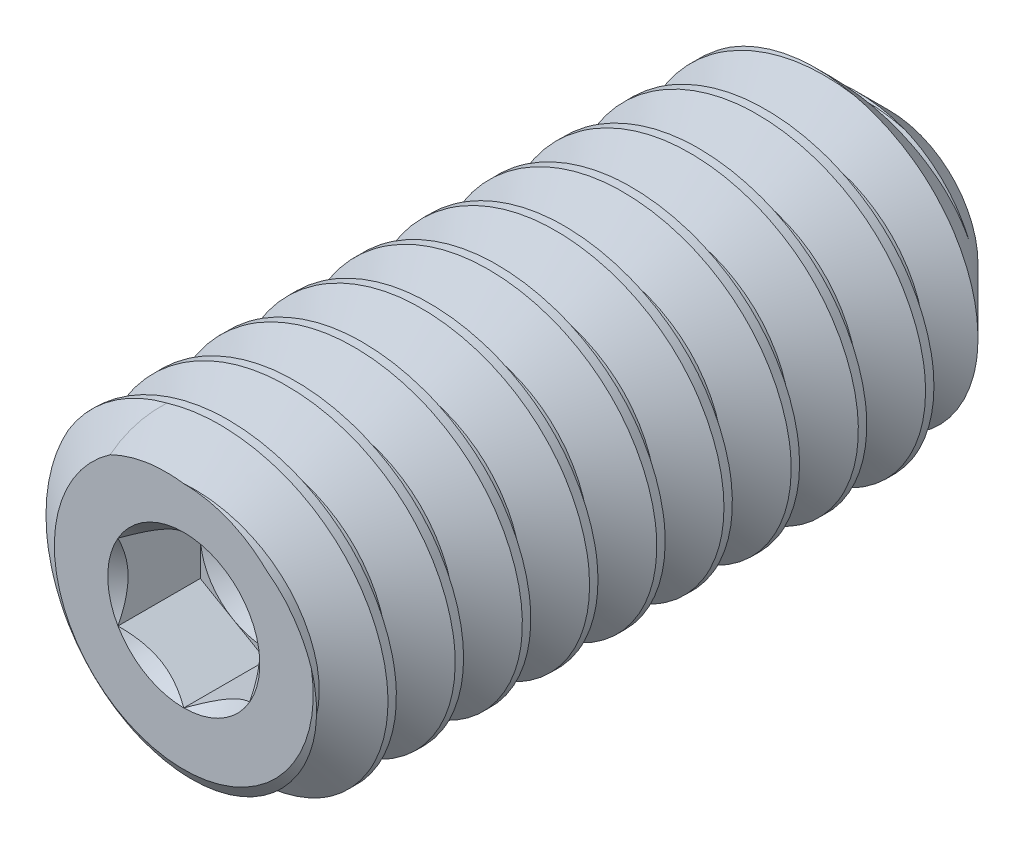
SolidWorks part; units mm, degrees
ref_plane "Front" through (0, 0, 0) normal (0, 0, 1) x (1, 0, 0)
ref_plane "Top" through (0, 0, 0) normal (0, 1, 0) x (1, 0, 0)
ref_plane "Right" through (0, 0, 0) normal (1, 0, 0) x (0, 0, -1)
sketch "Sketch22" plane through (0, 0, 0) normal (1, 0, 0) x (0, 0, -1)
  line L0 (-2.2014, 0) -> (-2.2014, 0.8738)
  line L1 (-2.2014, 0.8738) -> (-2.0485, 1.0922)
  line L2 (-2.0485, 1.0922) -> (2.0673, 1.0922)
  line L3 (2.0673, 1.0922) -> (2.5611, 0.5985)
  line L4 (2.5611, 0.5985) -> (2.2014, 0)
  line L5 (2.2014, 0) -> (-2.2014, 0)
  line L6 (2.2014, 0) -> (2.5611, 0) construction
  line L7 (2.5611, 0) -> (2.5611, 0.5985) construction
  line L8 (2.5611, -0.5985) -> (2.2014, 0) construction
  line L9 (-2.0485, -1.0922) -> (2.0673, -1.0922) construction
  dimension "Dia" = 2.1844
  dimension "Length" = 4.7625
  dimension "D3" = 35
  dimension "D5" = 118
  dimension "D6" = 45
  dimension "D7" = 1.7475
revolve "Revolve1" add sketch "Sketch22" angle 360 about L6
ref_plane "Plane1" through (0, 0, -2.5611) normal (0, 0, 1) x (1, 0, 0)
sketch "Sketch27" plane through (0, 0, -2.5611) normal (0, 0, 1) x (1, 0, 0)
  circle A0 centre (0, 0) radius 1.0922 construction
  circle A1 centre (0, 0) radius 1.0922
curve "Helix/Spiral1" pitch 0.4536 height 5.2161 radius 1.0922 centre (0, 0, -2.5611) axis (0, 0, 1) start towards (0, 1, 0)
sketch "Sketch28" plane through (0, 0, 0) normal (1, 0, 0) x (0, 0, -1)
  line L0 (2.5611, 1.0922) -> (2.9579, 1.0922)
  line L1 (2.9579, 1.0922) -> (2.7878, 0.7976)
  line L2 (2.7878, 0.7976) -> (2.7311, 0.7976)
  line L3 (2.7311, 0.7976) -> (2.5611, 1.0922)
  line L4 (2.6461, 0.9449) -> (2.8729, 0.9449) construction
  line L6 (-2.0485, 1.0922) -> (2.0673, 1.0922) construction
  line L7 (2.5611, 3.4925) -> (2.5611, -3.4925) construction
  dimension "D1" = 0.0567
  dimension "D2" = 0.2268
  dimension "D3" = 60
sweep "Cut-Sweep2" cut profiles "Sketch28" path "Helix/Spiral1"
sketch "Sketch23" plane through (0, 0, 2.2014) normal (0, 0, 1) x (1, 0, 0)
  line L1 (0, 0.5133) -> (-0.4445, 0.2566)
  line L2 (-0.4445, 0.2566) -> (-0.4445, -0.2566)
  line L3 (-0.4445, -0.2566) -> (0, -0.5133)
  line L4 (0, -0.5133) -> (0.4445, -0.2566)
  line L5 (0.4445, -0.2566) -> (0.4445, 0.2566)
  line L6 (0.4445, 0.2566) -> (0, 0.5133)
  circle A0 centre (0, 0) radius 0.4445 construction
  dimension "Hex" = 0.889
extrude "Cut-Extrude10" cut sketch "Sketch23" against normal blind 0.5556
sketch "Sketch24" plane through (0, 0, 2.2014) normal (0, 0, 1) x (1, 0, 0)
  circle A0 centre (0, 0) radius 0.5133
extrude "Cut-Extrude11" cut sketch "Sketch24" against normal through all draft 45
sketch "Sketch26" plane through (0, 0, 1.6458) normal (0, 0, 1) x (1, 0, 0)
  circle A0 centre (0, 0) radius 0.4445 construction
  circle A1 centre (0, 0) radius 0.4445
extrude "Cut-Extrude12" cut sketch "Sketch26" against normal through all draft 60
sketch "Sketch30" plane through (0, 0, 0) normal (1, 0, 0) x (0, 0, -1)
  line L0 (-2.0485, 1.0922) -> (2.0673, 1.0922) construction
  line L1 (-2.2014, 0) -> (-2.2014, 0.8738) construction
  line L2 (2.5611, 0) -> (2.5611, 0.5985) construction
  line L3 (-2.0485, -1.0922) -> (2.0673, -1.0922) construction
  point P0 (-2.2014, 1.0922)
  point P1 (2.5611, 1.0922)
  point P2 (2.5611, -1.0922)
  point P11 (1.4271, -1.0922)
  dimension "D1" = 1.1339
sketch "Sketch31" plane through (0, 0, 0) normal (1, 0, 0) x (0, 0, -1)
  line L2 (2.2014, 0) -> (2.5611, -0.5985)
  line L3 (2.5611, 0.5985) -> (2.2014, 0)
equation "\"D7@Sketch22\"=\"Dia@Sketch22\"*.8"
equation "\"D1@Sketch28\" = \"D4@Helix/Spiral1\" * .125"
equation "\"D3@Helix/Spiral1\" = \"Length@Sketch22\" + \"D4@Helix/Spiral1\""
equation "\"D1@Sketch30\" = \"D4@Helix/Spiral1\" * 2.5"
equation "\"hex Depth@Cut-Extrude10\" = \"Hex@Sketch23\" * .625"
equation "\"D2@Sketch28\" = \"D4@Helix/Spiral1\" * .5"
